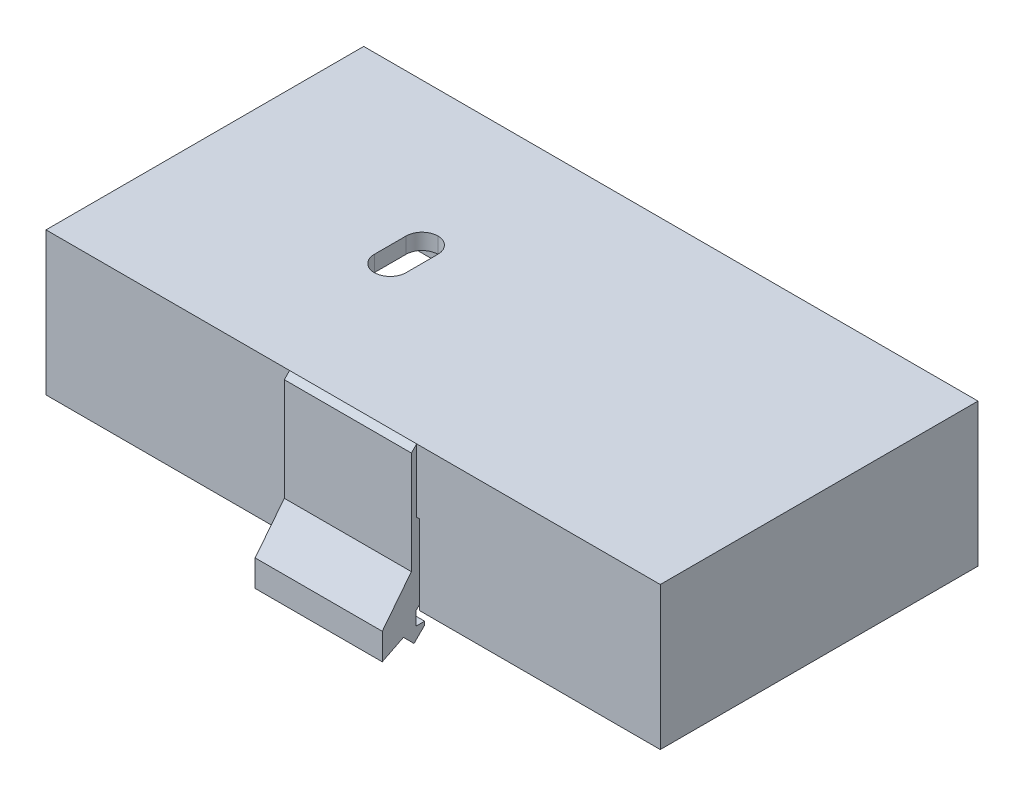
SolidWorks part; units mm, degrees
ref_plane "Front Plane" through (0, 0, 0) normal (0, 0, 1) x (1, 0, 0)
ref_plane "Top Plane" through (0, 0, 0) normal (0, 1, 0) x (1, 0, 0)
ref_plane "Right Plane" through (0, 0, 0) normal (1, 0, 0) x (0, 0, -1)
sketch "Sketch1" plane through (0, 9.8203, 0) normal (0, 1, 0) x (1, 0, 0)
  line L1 (-55, -27) -> (55, -27)
  line L2 (-55, -27) -> (-55, 27)
  line L3 (-55, 27) -> (55, 27)
  line L4 (55, -27) -> (55, 27)
  line L5 (-55, -27) -> (55, 27) construction
  line L6 (-55, 27) -> (55, -27) construction
  line L7 (-58, -30) -> (58, -30)
  line L8 (-58, -30) -> (-58, 30)
  line L9 (-58, 30) -> (58, 30)
  line L10 (58, -30) -> (58, 30)
  line L11 (-58, -30) -> (58, 30) construction
  line L12 (-58, 30) -> (58, -30) construction
  point P0 (0, 0)
  point P7 (0, 0)
  point P13 (51.5631, 23.6541)
  point P15 (55, 27)
extrude "Boss-Extrude1" add sketch "Sketch1" along normal offset from surface (24 mm away) 34 offset beyond the face yes
sketch "Sketch2" plane through (0, 33.8203, 0) normal (0, 1, 0) x (1, 0, 0)
  line L1 (58, -30) -> (-58, -30)
  line L2 (58, -30) -> (58, 30)
  line L3 (58, 30) -> (-58, 30)
  line L4 (-58, -30) -> (-58, 30)
  line L5 (58, -30) -> (-58, 30) construction
  line L6 (58, 30) -> (-58, -30) construction
  point P0 (0, 0)
extrude "Boss-Extrude2" add sketch "Sketch2" along normal blind 3
sketch "Sketch3" plane through (0, 0, 0) normal (1, 0, 0) x (0, 0, -1)
  line L0 (28.5, 9.8203) -> (28.5, 23.3203)
  line L1 (-30, 9.8203) -> (30, 9.8203) construction
  line L2 (28.5, 23.3203) -> (30, 24.8203)
  line L3 (30, 36.8203) -> (30, 9.8203) construction
  line L4 (30, 24.8203) -> (30, 9.8203)
  line L5 (30, 9.8203) -> (28.5, 9.8203)
  dimension "D1" = 1.5
  dimension "D2" = 45
  dimension "D3" = 15
extrude "Cut-Extrude1" cut sketch "Sketch3" against normal mid plane 25
sketch "Sketch4" plane through (0, 0, 0) normal (1, 0, 0) x (0, 0, -1)
  line L1 (30.1, 7.0703) -> (28.5, 7.0703)
  line L2 (28.5, 7.0703) -> (28.5, 6.4203)
  line L3 (28.5, 6.4203) -> (30.5, 4.4203)
  line L7 (31, 16.4203) -> (31, 35.8203)
  line L8 (28.5, 6.3203) -> (28.5, 7.3203) construction
  line L9 (28.5, 7.3203) -> (30, 7.3203) construction
  line L12 (30.5, 4.4203) -> (31.3531, 4.4203) construction
  line L14 (30, 4.8203) -> (28.5, 6.3203) construction
  line L15 (31, 35.8203) -> (30, 36.8203)
  line L16 (30, 36.8203) -> (29, 36.8203)
  line L18 (-30, 36.8203) -> (30, 36.8203) construction
  line L19 (30.1, 7.0703) -> (30.1, 9.6345)
  line L20 (30.1, 9.6345) -> (29, 10.7345)
  line L21 (29, 10.7345) -> (29, 36.8203)
  line L23 (30, 8.3203) -> (28.5, 9.8203) construction
  line L24 (30, 36.8203) -> (30, 9.8203) construction
  line L25 (30, 9.8203) -> (30, 1.8203) construction
  line L26 (30.5, 4.4203) -> (32.5, 6.4203)
  line L27 (32.5, 6.4203) -> (36.5, 4.4203)
  line L28 (36.5, 4.4203) -> (36.5, 9.4203)
  line L29 (36.5, 9.4203) -> (31, 16.4203)
  point P6 (0, 0)
  point P29 (36.5, 9.8142)
  point P34 (31, 18.4462)
  point P35 (31, 17.5941)
  point P36 (0, 0)
  point P37 (30.3395, 37)
  dimension "D2" = 0.25
  dimension "D3" = 0.1
  dimension "D4" = 1
  dimension "D5" = 0.5
  dimension "D6" = 0.5
  dimension "D7" = 0.1
  dimension "D8" = 5
  dimension "D9" = 1
  dimension "D10" = 45
  dimension "D11" = 6
  dimension "D12" = 45
  dimension "D13" = 2
  dimension "D14" = 7
extrude "Boss-Extrude3" add sketch "Sketch4" along normal mid plane 24
sketch "Sketch5" plane through (0, 9.8203, 0) normal (0, -1, 0) x (1, 0, 0)
  line L5 (-56.5, 28.5) -> (-12.5, 28.5) construction
  line L6 (56.7, -28.7) -> (-56.7, -28.7)
  line L7 (56.7, -28.7) -> (56.7, 28.7)
  line L8 (56.7, 28.7) -> (-56.7, 28.7)
  line L9 (-56.7, -28.7) -> (-56.7, 28.7)
  line L10 (56.7, -28.7) -> (-56.7, 28.7) construction
  line L11 (56.7, 28.7) -> (-56.7, -28.7) construction
  line L12 (-56.5, -28.5) -> (-56.5, 28.5) construction
  line L14 (55, -27) -> (-55, -27)
  line L15 (55, -27) -> (55, 27)
  line L16 (55, 27) -> (-55, 27)
  line L17 (-55, -27) -> (-55, 27)
  line L18 (55, -27) -> (-55, 27) construction
  line L19 (55, 27) -> (-55, -27) construction
  point P0 (0, 0)
  point P1 (0, 0)
  point P11 (0, 0)
  dimension "D1" = 0.2
  dimension "D2" = 0.2
extrude "Cut-Extrude2" cut sketch "Sketch5" against normal blind 5.5
mirror "Mirror1" about plane through (0, 0, 0) normal (0, 0, 1) of "Cut-Extrude1", "Boss-Extrude3"
sketch "Sketch6" plane through (0, 36.8203, 0) normal (0, 1, 0) x (1, 0, 0)
  line L1 (-23, 6) -> (-17, 6)
  line L2 (-23, 6) -> (-23, -6)
  line L3 (-23, -6) -> (-17, -6)
  line L4 (-17, 6) -> (-17, -6)
  line L5 (-23, 6) -> (-17, -6) construction
  line L6 (-23, -6) -> (-17, 6) construction
  point P0 (-20, 0)
  point P5 (0, 0)
  dimension "D1" = 6
  dimension "D2" = 12
  dimension "D3" = 20
extrude "Cut-Extrude3" cut sketch "Sketch6" against normal up to next
fillet "Fillet3" radius 3 4 edges at (-23, 35.3203, 6) (-17, 35.3203, 6) (-17, 35.3203, -6) (-23, 35.3203, -6)
